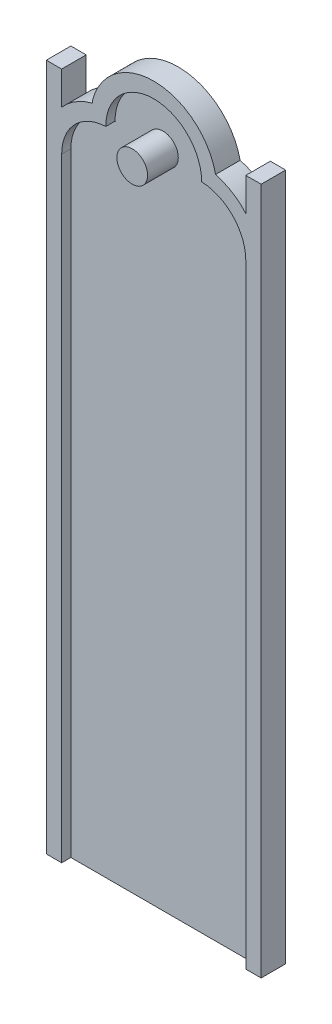
SolidWorks part; units mm, degrees
material "Default"
ref_plane "Front Plane" through (0, 0, 0) normal (0, 0, 1) x (1, 0, 0)
ref_plane "Top Plane" through (0, 0, 0) normal (0, 1, 0) x (1, 0, 0)
ref_plane "Right Plane" through (0, 0, 0) normal (1, 0, 0) x (0, 0, -1)
sketch "Sketch2" plane through (0, 0, 0) normal (0, 0, 1) x (1, 0, 0)
  line L0 (-333.7819, -1512.0628) -> (366.2181, -1512.0628)
  line L1 (366.2181, -1512.0628) -> (366.2181, 487.9372)
  line L2 (-333.7819, -1512.0628) -> (-333.7819, 487.9372)
  line L9 (-133.7819, 637.9372) -> (-139.9372, 637.9372)
  line L11 (-183.7819, 687.9372) -> (-183.7819, 681.5864)
  line L16 (-283.7819, 727.9372) -> (-333.7819, 727.9372)
  line L17 (-183.7819, 681.5864) -> (-183.7819, 687.9372)
  line L18 (166.2181, 637.9372) -> (172.3734, 637.9372)
  line L19 (-139.9372, 637.9372) -> (-139.6601, 637.9372)
  line L20 (-283.7819, 727.9372) -> (-283.7819, 620.2248)
  line L21 (-333.7819, 487.9372) -> (-333.7819, 727.9372)
  line L23 (366.2181, 727.9372) -> (316.2181, 727.9372)
  line L24 (316.2181, 727.9372) -> (316.2181, 620.2248)
  line L25 (366.2181, 727.9372) -> (366.2181, 487.9372)
  line L26 (-283.7819, 487.9372) -> (-283.7819, -1512.0628)
  line L27 (316.2181, 487.9372) -> (316.2181, -1512.0628)
  line L28 (316.2181, -1512.0628) -> (316.2181, 487.9372)
  arc A4 (-183.7819, 681.5864) -> (-283.7819, 620.2248) centre (-133.7819, 487.9372) ccw
  arc A6 (-133.7819, 637.9372) -> (-283.7819, 487.9372) centre (-133.7819, 487.9372) ccw
  arc A7 (316.2181, 487.9372) -> (166.2181, 637.9372) centre (166.2181, 487.9372) ccw
  arc A11 (316.2181, 620.2248) -> (217.7884, 681.1741) centre (166.2181, 487.9372) ccw
  circle A12 centre (16.2181, 637.9372) radius 50
  circle A13 centre (16.2181, 637.9372) radius 20
  arc A14 (217.7884, 681.1741) -> (-185.3522, 681.1741) centre (16.2181, 637.9372) ccw
  arc A15 (172.3733, 637.8108) -> (-139.9371, 637.8108) centre (16.2181, 637.9372) ccw
  dimension "D1" = 700
  dimension "D2" = 2000
extrude "Boss-Extrude3" add sketch "Sketch2" along normal blind 50 contours L18 A15 L9 A6 L26 L0 L27 A7 A12 region at (16.2181, -417.8275, 0)
extrude "Boss-Extrude4" add sketch "Sketch2<8>" along normal blind 80 contours A15 A7 L27 L0 L1 A11 A14 L11 A4 L2 L26 A6 region at (-309.2025, -512.0628, 0)
sketch "Sketch2<8>" plane through (0, 0, 0) normal (0, 0, 1) x (1, 0, 0) same geometry as "Sketch2"
sketch "Sketch4" plane through (0, 0, 0) normal (0, 0, 1) x (1, 0, 0)
extrude "Boss-Extrude5" add sketch "Sketch2<9>" along normal blind 150 contours A12 A13 | A13 region at (-32.3677, 637.9372, 0) region at (16.2181, 637.9372, 0)
sketch "Sketch2<9>" plane through (0, 0, 0) normal (0, 0, 1) x (1, 0, 0) same geometry as "Sketch2"
sketch "Sketch6" plane through (0, 0, 0) normal (0, 0, 1) x (1, 0, 0)
sketch "Sketch7" plane through (0, 0, 0) normal (1, 0, 0) x (0, 0, -1)
  line L20 (-999.3996, -817.6379) -> (-670.0663, -817.6379) construction
sketch "Sketch10" plane through (0, 0, 0) normal (1, 0, 0) x (0, 0, -1)
ref_plane "Plane1" through (366.2181, -1512.0628, 80) normal (0, 1, 0) x (1, 0, 0)
sketch "Sketch22" plane through (366.2181, 0, 0) normal (1, 0, 0) x (0, 0, -1)
